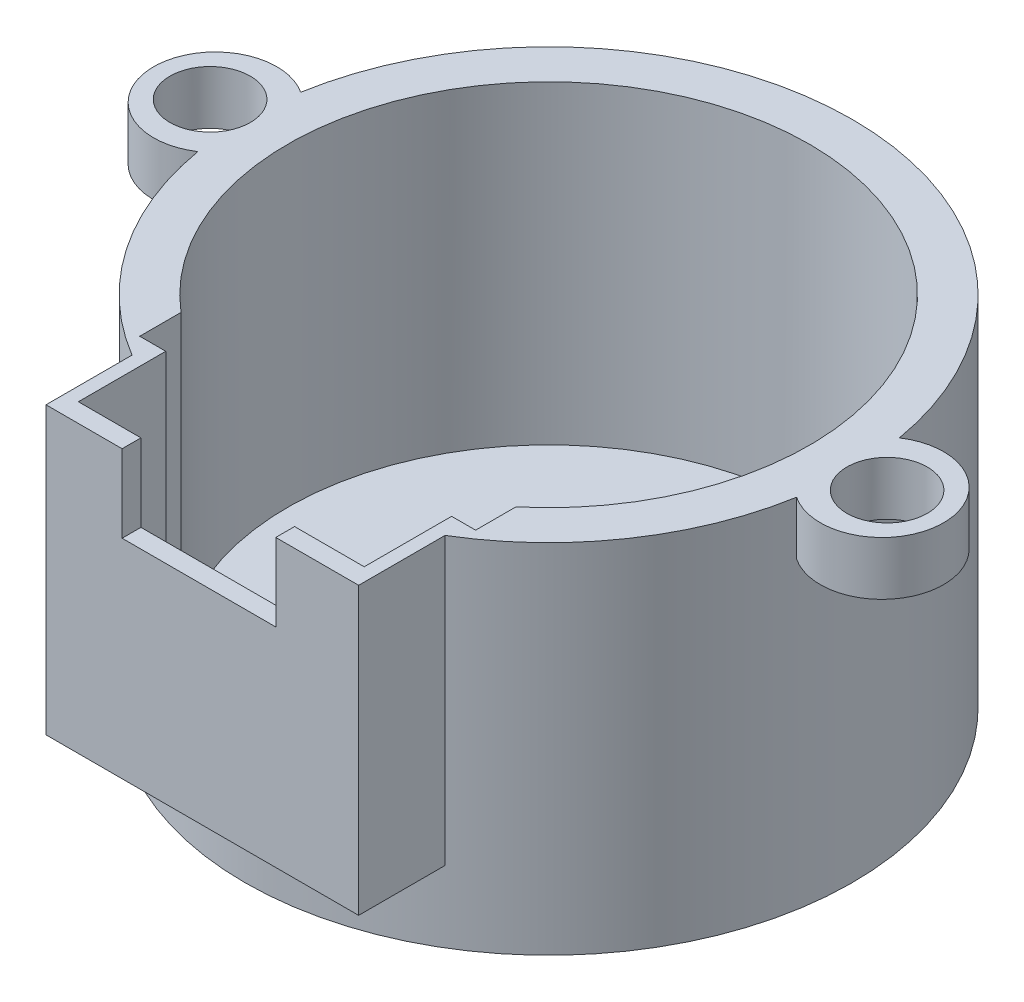
SolidWorks part; units mm, degrees
ref_plane "Front Plane" through (0, 0, 0) normal (0, 0, 1) x (1, 0, 0)
ref_plane "Top Plane" through (0, 0, 0) normal (0, 1, 0) x (1, 0, 0)
ref_plane "Right Plane" through (0, 0, 0) normal (1, 0, 0) x (0, 0, -1)
sketch "Sketch1" plane through (0, 0, 0) normal (0, 1, 0) x (1, 0, 0)
  circle A0 centre (0, 0) radius 17
  dimension "D1" = 34
extrude "Boss-Extrude1" add sketch "Sketch1" along normal blind 20
shell "Shell1" thickness 2.4 removed face at (0, 20, 17)
sketch "Sketch2" plane through (0, 20, 0) normal (0, 1, 0) x (1, 0, 0)
  line L0 (-14.6, 0) -> (37.717, 0) construction
  line L1 (0, 0) -> (0, -36.0151) construction
  circle A0 centre (0, 0) radius 14.6 construction
  circle A3 centre (18.6594, 0) radius 3.45
  circle A4 centre (-18.6594, 0) radius 3.45
extrude "Boss-Extrude3" add sketch "Sketch2" against normal blind 3
sketch "Sketch4" plane through (0, 20, 0) normal (0, 1, 0) x (1, 0, 0)
  line L0 (0, 0) -> (0, -29.7272) construction
  circle A0 centre (18.9465, 0) radius 2.25
  circle A1 centre (-18.9465, 0) radius 2.25
  dimension "D1" = 4.5
extrude "Cut-Extrude1" cut sketch "Sketch4" against normal blind 3
sketch "Sketch5" plane through (0, 20, 0) normal (0, 1, 0) x (1, 0, 0)
  line L1 (-8.7324, -11.7006) -> (8.7676, -11.7006)
  line L2 (-8.7324, -11.7006) -> (-8.7324, -19.4006)
  line L3 (-8.7324, -19.4006) -> (8.7676, -19.4006)
  line L4 (8.7676, -11.7006) -> (8.7676, -19.4006)
  circle A0 centre (0, 0) radius 14.6 construction
  dimension "D1" = 17.5
  dimension "D2" = 7.7
extrude "Boss-Extrude4" add sketch "Sketch5" against normal blind 16
sketch "Sketch6" plane through (0, 20, 0) normal (0, 1, 0) x (1, 0, 0)
  line L1 (-7.974, -18.3476) -> (8.026, -18.3476)
  line L2 (-7.974, -18.3476) -> (-7.974, -9.7476)
  line L3 (-7.974, -9.7476) -> (8.026, -9.7476)
  line L4 (8.026, -18.3476) -> (8.026, -9.7476)
  dimension "D1" = 16
  dimension "D2" = 8.6
extrude "Cut-Extrude2" cut sketch "Sketch6" against normal blind 14
sketch "Sketch7" plane through (0, 0, 19.4006) normal (0, 0, 1) x (1, 0, 0)
  line L1 (-4.4725, 15.661) -> (4.1275, 15.661)
  line L2 (-4.4725, 15.661) -> (-4.4725, 21.461)
  line L3 (-4.4725, 21.461) -> (4.1275, 21.461)
  line L4 (4.1275, 15.661) -> (4.1275, 21.461)
  dimension "D1" = 8.6
  dimension "D2" = 5.8
extrude "Cut-Extrude3" cut sketch "Sketch7" against normal blind 5
fillet "Fillet4" radius 1 1 edges at (0, 4, 11.7006)
sketch "Sketch8" plane through (0, 20, 0) normal (0, 1, 0) x (1, 0, 0)
  line L1 (-9.4317, -13.4558) -> (9.3683, -13.4558)
  line L2 (-9.4317, -13.4558) -> (-9.4317, -10.4558)
  line L3 (-9.4317, -10.4558) -> (9.3683, -10.4558)
  line L4 (9.3683, -13.4558) -> (9.3683, -10.4558)
  point P4 (9.6294, -13.0206)
  dimension "D1" = 18.8
  dimension "D2" = 3
extrude "Cut-Extrude4" cut sketch "Sketch8" against normal blind 16
